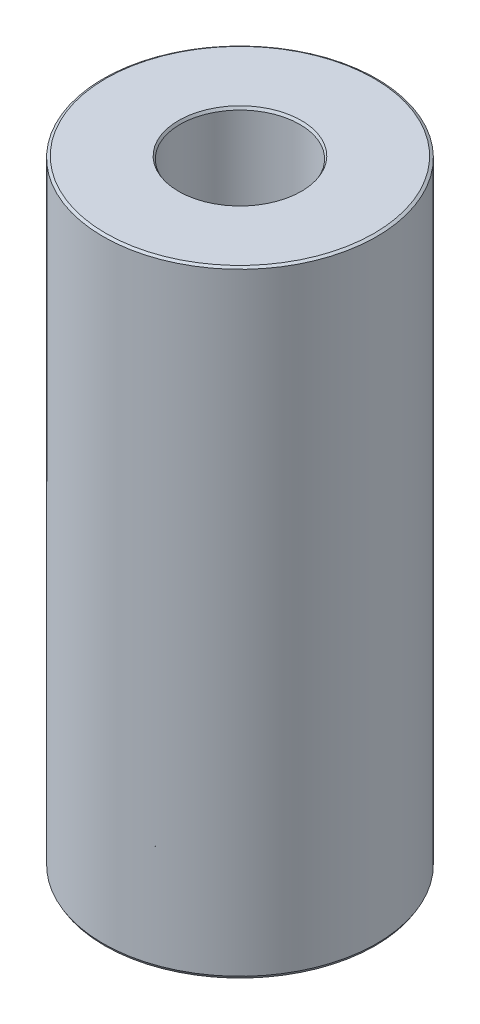
SolidWorks part; units mm, degrees
ref_plane "Front Plane" through (0, 0, 0) normal (0, 0, 1) x (1, 0, 0)
ref_plane "Top Plane" through (0, 0, 0) normal (0, 1, 0) x (1, 0, 0)
ref_plane "Right Plane" through (0, 0, 0) normal (1, 0, 0) x (0, 0, -1)
sketch "Sketch1" plane through (0, 0, 0) normal (0, 1, 0) x (1, 0, 0)
  circle A0 centre (0, 0) radius 32.5
  dimension "SLEEVE_OD" = 65
extrude "Boss-Extrude1" add sketch "Sketch1" along normal blind 146.4755
sketch "Sketch2" plane through (0, 0, 0) normal (0, 1, 0) x (1, 0, 0)
  circle A0 centre (0, 0) radius 14.2342
  dimension "BORE_D" = 28.4684
extrude "Cut-Extrude1" cut sketch "Sketch2" along normal through all
chamfer "Chamfer1" distance 0.3606 angle 60 4 edges at (0, 146.4755, 14.2342) (0, 0, 14.2342) (0, 0, 32.5) (0, 146.4755, 32.5) first distance on face at (0, 146.4755, 14.2342) first distance on face at (0, 0, 14.2342) first distance on face at (0, 146.4755, 32.5)
